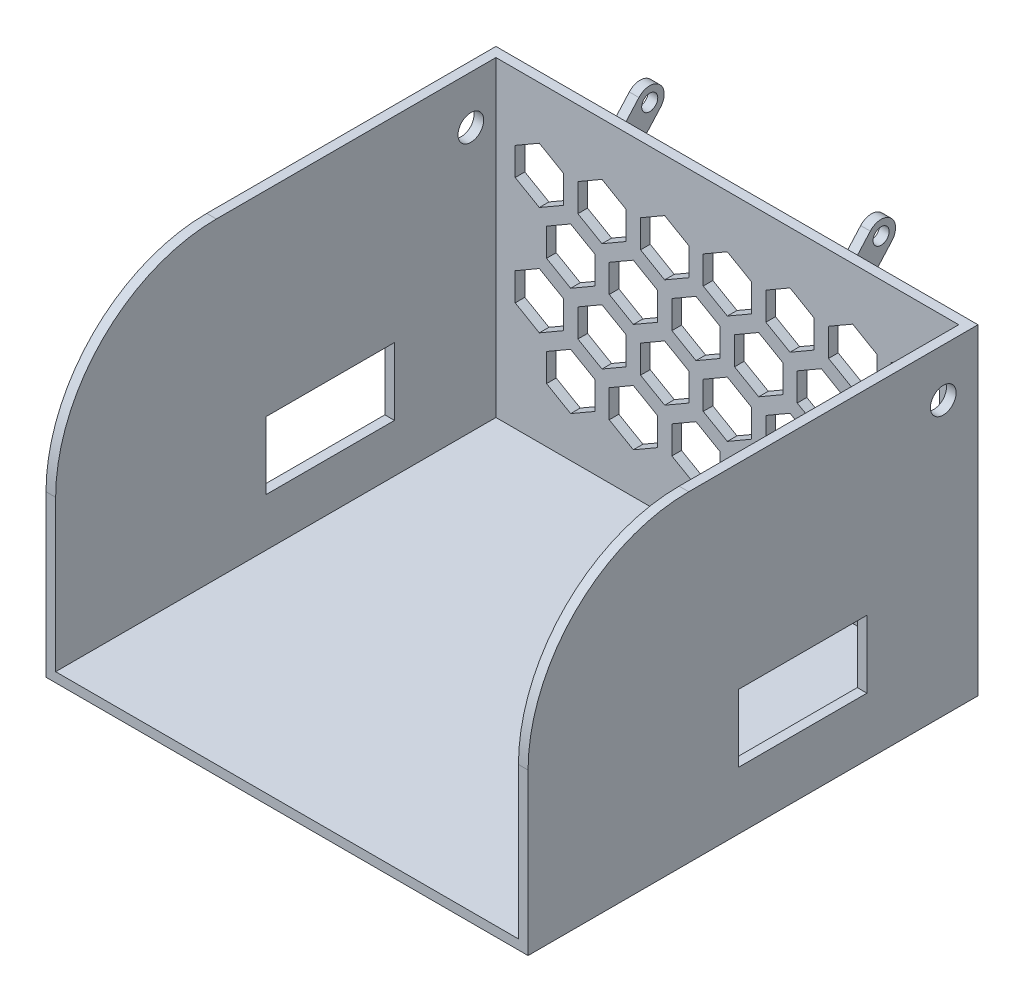
SolidWorks part; units mm, degrees
material "PLA"
ref_plane "Front Plane" through (0, 0, 0) normal (0, 0, 1) x (1, 0, 0)
ref_plane "Top Plane" through (0, 0, 0) normal (0, 1, 0) x (1, 0, 0)
ref_plane "Right Plane" through (0, 0, 0) normal (1, 0, 0) x (0, 0, -1)
sketch "Sketch1" plane through (0, 0, 0) normal (1, 0, 0) x (0, 0, -1)
  line L0 (0, 0) -> (-140, 0)
  line L1 (-140, 0) -> (-140, 50)
  line L2 (-90, 100) -> (0, 100)
  line L3 (0, 100) -> (0, 0)
  arc A0 (-140, 50) -> (-90, 100) centre (-90, 50) cw
  dimension "D1" = 140
  dimension "D2" = 100
  dimension "D3" = 50
extrude "Boss-Extrude1" add sketch "Sketch1" along normal blind 150 contours A0 L2 L3 L0 L1
sketch "Sketch2" plane through (0, 100, 0) normal (0, 1, 0) x (1, 0, 0)
  line L0 (150, 0) -> (0, 0) construction
  line L1 (3, -3) -> (147, -3)
  line L2 (3, -3) -> (3, -145)
  line L3 (3, -145) -> (147, -145)
  line L4 (147, -3) -> (147, -145)
  line L5 (150, -90) -> (150, 0) construction
  line L6 (0, -90) -> (0, 0) construction
  line L8 (150, -140) -> (0, -140) construction
  dimension "D1" = 3
  dimension "D2" = 3
  dimension "D3" = 3
  dimension "D4" = 5
extrude "Cut-Extrude1" cut sketch "Sketch2" against normal offset from surface (97 mm away) 3 up to face at (75, 0, 70)
ref_plane "Plane1" through (75, 0, 0) normal (1, 0, 0) x (0, 0, -1)
ref_plane "Plane2" through (111, 0, 0) normal (1, 0, 0) x (0, 0, -1)
ref_plane "Plane3" through (39, 0, 0) normal (1, 0, 0) x (0, 0, -1)
sketch "Sketch3" plane through (111, 0, 0) normal (1, 0, 0) x (0, 0, -1)
  line L0 (0, 100) -> (0, 86.4837)
  line L1 (0, 86.4837) -> (10.7098, 98.4837)
  line L2 (3.9952, 104.4764) -> (0, 100)
  arc A0 (10.7098, 98.4837) -> (3.9952, 104.4764) centre (7.3525, 101.4801) ccw
  circle A1 centre (7.3525, 101.4801) radius 2.5
  dimension "D1" = 2
  dimension "D2" = 5
  dimension "D3" = 6
  dimension "D4" = 12
extrude "Boss-Extrude2" add sketch "Sketch3" along normal mid plane 3
mirror "Mirror1" about plane through (75, 0, 0) normal (1, 0, 0) of "Boss-Extrude2"
sketch "Sketch4" plane through (150, 0, 0) normal (1, 0, 0) x (0, 0, -1)
  line L0 (-10.8107, 85.0634) -> (-67.3793, 28.4949) construction
  line L1 (-74.5612, 38.9949) -> (-74.5612, 17.9949)
  line L2 (-74.5612, 17.9949) -> (-34.5612, 17.9949)
  line L3 (0, 0) -> (-140, 0) construction
  line L4 (-34.5612, 17.9949) -> (-34.5612, 38.9949)
  line L5 (-34.5612, 38.9949) -> (-74.5612, 38.9949)
  circle A0 centre (-67.3793, 28.4949) radius 2.5
  circle A1 centre (-10.8107, 85.0634) radius 4
  point P8 (-74.5612, 28.4949)
  dimension "D4" = 8
  dimension "D5" = 5
  dimension "D1" = 80
  dimension "D2" = 45
  dimension "D3" = 40
  dimension "D6" = 21
extrude "Cut-Extrude2" cut sketch "Sketch4" against normal up to next contours A0 | A1 | L4 L5 A0 L1 L2 region at (150, 28.4949, 54.2544) region at (150, 28.4949, 67.3793) region at (150, 85.0634, 10.8107)
mirror "Mirror2" about plane through (75, 0, 0) normal (1, 0, 0) of "Cut-Extrude2"
sketch "Sketch5" plane through (0, 0, 0) normal (0, 0, -1) x (-1, 0, 0)
  line L0 (-150, 75) -> (0, 75) construction
  line L1 (-150, 100) -> (-150, 0) construction
  line L2 (0, 100) -> (0, 0) construction
  line L3 (-75, 100) -> (-75, 0) construction
  line L4 (-109.5, 100) -> (-40.5, 100) construction
  line L5 (-75, 91.3518) -> (-75, -91.3518) construction
  line L6 (-114, 83.6603) -> (-121.5, 79.3301)
  line L7 (-133.5, 83.6603) -> (-141, 79.3301)
  line L8 (-141, 79.3301) -> (-141, 70.6699)
  line L9 (-141, 70.6699) -> (-133.5, 66.3397)
  line L10 (-133.5, 66.3397) -> (-126, 70.6699)
  line L11 (-126, 70.6699) -> (-126, 79.3301)
  line L12 (-126, 79.3301) -> (-133.5, 83.6603)
  line L13 (-121.5, 79.3301) -> (-121.5, 70.6699)
  line L14 (-121.5, 70.6699) -> (-114, 66.3397)
  line L15 (-114, 66.3397) -> (-106.5, 70.6699)
  line L16 (-106.5, 70.6699) -> (-106.5, 79.3301)
  line L17 (-106.5, 79.3301) -> (-114, 83.6603)
  line L18 (-94.5, 83.6603) -> (-102, 79.3301)
  line L19 (-102, 79.3301) -> (-102, 70.6699)
  line L20 (-102, 70.6699) -> (-94.5, 66.3397)
  line L21 (-94.5, 66.3397) -> (-87, 70.6699)
  line L22 (-87, 70.6699) -> (-87, 79.3301)
  line L23 (-87, 79.3301) -> (-94.5, 83.6603)
  line L24 (-75, 83.6603) -> (-82.5, 79.3301)
  line L25 (-82.5, 79.3301) -> (-82.5, 70.6699)
  line L26 (-82.5, 70.6699) -> (-75, 66.3397)
  line L27 (-75, 66.3397) -> (-67.5, 70.6699)
  line L28 (-67.5, 70.6699) -> (-67.5, 79.3301)
  line L29 (-67.5, 79.3301) -> (-75, 83.6603)
  line L30 (-55.5, 83.6603) -> (-63, 79.3301)
  line L31 (-63, 79.3301) -> (-63, 70.6699)
  line L32 (-63, 70.6699) -> (-55.5, 66.3397)
  line L33 (-55.5, 66.3397) -> (-48, 70.6699)
  line L34 (-48, 70.6699) -> (-48, 79.3301)
  line L35 (-48, 79.3301) -> (-55.5, 83.6603)
  line L36 (-36, 83.6603) -> (-43.5, 79.3301)
  line L37 (-43.5, 79.3301) -> (-43.5, 70.6699)
  line L38 (-43.5, 70.6699) -> (-36, 66.3397)
  line L39 (-36, 66.3397) -> (-28.5, 70.6699)
  line L40 (-28.5, 70.6699) -> (-28.5, 79.3301)
  line L41 (-28.5, 79.3301) -> (-36, 83.6603)
  line L42 (-16.5, 83.6603) -> (-24, 79.3301)
  line L43 (-24, 79.3301) -> (-24, 70.6699)
  line L44 (-24, 70.6699) -> (-16.5, 66.3397)
  line L45 (-16.5, 66.3397) -> (-9, 70.6699)
  line L46 (-9, 70.6699) -> (-9, 79.3301)
  line L47 (-9, 79.3301) -> (-16.5, 83.6603)
  line L48 (-150, 58.1125) -> (0, 58.1125) construction
  line L49 (-123.75, 58.1125) -> (-123.75, 75) construction
  line L50 (-123.75, 66.7728) -> (-131.25, 62.4426)
  line L51 (-131.25, 62.4426) -> (-131.25, 53.7824)
  line L52 (-131.25, 53.7824) -> (-123.75, 49.4523)
  line L53 (-123.75, 49.4523) -> (-116.25, 53.7824)
  line L54 (-116.25, 53.7824) -> (-116.25, 62.4426)
  line L55 (-116.25, 62.4426) -> (-123.75, 66.7728)
  line L56 (-37.5, 100) -> (0, 100) construction
  line L57 (-104.25, 66.7728) -> (-111.75, 62.4426)
  line L58 (-111.75, 62.4426) -> (-111.75, 53.7824)
  line L59 (-111.75, 53.7824) -> (-104.25, 49.4523)
  line L60 (-104.25, 49.4523) -> (-96.75, 53.7824)
  line L61 (-96.75, 53.7824) -> (-96.75, 62.4426)
  line L62 (-96.75, 62.4426) -> (-104.25, 66.7728)
  line L63 (-84.75, 66.7728) -> (-92.25, 62.4426)
  line L64 (-92.25, 62.4426) -> (-92.25, 53.7824)
  line L65 (-92.25, 53.7824) -> (-84.75, 49.4523)
  line L66 (-84.75, 49.4523) -> (-77.25, 53.7824)
  line L67 (-77.25, 53.7824) -> (-77.25, 62.4426)
  line L68 (-77.25, 62.4426) -> (-84.75, 66.7728)
  line L69 (-65.25, 66.7728) -> (-72.75, 62.4426)
  line L70 (-72.75, 62.4426) -> (-72.75, 53.7824)
  line L71 (-72.75, 53.7824) -> (-65.25, 49.4523)
  line L72 (-65.25, 49.4523) -> (-57.75, 53.7824)
  line L73 (-57.75, 53.7824) -> (-57.75, 62.4426)
  line L74 (-57.75, 62.4426) -> (-65.25, 66.7728)
  line L75 (-45.75, 66.7728) -> (-53.25, 62.4426)
  line L76 (-53.25, 62.4426) -> (-53.25, 53.7824)
  line L77 (-53.25, 53.7824) -> (-45.75, 49.4523)
  line L78 (-45.75, 49.4523) -> (-38.25, 53.7824)
  line L79 (-38.25, 53.7824) -> (-38.25, 62.4426)
  line L80 (-38.25, 62.4426) -> (-45.75, 66.7728)
  line L81 (-26.25, 66.7728) -> (-33.75, 62.4426)
  line L82 (-33.75, 62.4426) -> (-33.75, 53.7824)
  line L83 (-33.75, 53.7824) -> (-26.25, 49.4523)
  line L84 (-26.25, 49.4523) -> (-18.75, 53.7824)
  line L85 (-18.75, 53.7824) -> (-18.75, 62.4426)
  line L86 (-18.75, 62.4426) -> (-26.25, 66.7728)
  line L87 (-9, 36.8949) -> (-16.5, 32.5648)
  line L88 (-9, 45.5551) -> (-9, 36.8949)
  line L89 (-16.5, 49.8853) -> (-9, 45.5551)
  line L90 (-24, 45.5551) -> (-16.5, 49.8853)
  line L91 (-24, 36.8949) -> (-24, 45.5551)
  line L92 (-16.5, 32.5648) -> (-24, 36.8949)
  line L93 (-28.5, 36.8949) -> (-36, 32.5648)
  line L94 (-28.5, 45.5551) -> (-28.5, 36.8949)
  line L95 (-36, 49.8853) -> (-28.5, 45.5551)
  line L96 (-43.5, 45.5551) -> (-36, 49.8853)
  line L97 (-43.5, 36.8949) -> (-43.5, 45.5551)
  line L98 (-36, 32.5648) -> (-43.5, 36.8949)
  line L99 (-48, 36.8949) -> (-55.5, 32.5648)
  line L100 (-48, 45.5551) -> (-48, 36.8949)
  line L101 (-55.5, 49.8853) -> (-48, 45.5551)
  line L102 (-63, 45.5551) -> (-55.5, 49.8853)
  line L103 (-63, 36.8949) -> (-63, 45.5551)
  line L104 (-55.5, 32.5648) -> (-63, 36.8949)
  line L105 (-67.5, 36.8949) -> (-75, 32.5648)
  line L106 (-67.5, 45.5551) -> (-67.5, 36.8949)
  line L107 (-75, 49.8853) -> (-67.5, 45.5551)
  line L108 (-82.5, 45.5551) -> (-75, 49.8853)
  line L109 (-82.5, 36.8949) -> (-82.5, 45.5551)
  line L110 (-75, 32.5648) -> (-82.5, 36.8949)
  line L111 (-87, 36.8949) -> (-94.5, 32.5648)
  line L112 (-87, 45.5551) -> (-87, 36.8949)
  line L113 (-94.5, 49.8853) -> (-87, 45.5551)
  line L114 (-102, 45.5551) -> (-94.5, 49.8853)
  line L115 (-102, 36.8949) -> (-102, 45.5551)
  line L116 (-94.5, 32.5648) -> (-102, 36.8949)
  line L117 (-106.5, 36.8949) -> (-114, 32.5648)
  line L118 (-106.5, 45.5551) -> (-106.5, 36.8949)
  line L119 (-114, 49.8853) -> (-106.5, 45.5551)
  line L120 (-121.5, 45.5551) -> (-114, 49.8853)
  line L121 (-121.5, 36.8949) -> (-121.5, 45.5551)
  line L122 (-114, 32.5648) -> (-121.5, 36.8949)
  line L123 (-126, 36.8949) -> (-133.5, 32.5648)
  line L124 (-126, 45.5551) -> (-126, 36.8949)
  line L125 (-133.5, 49.8853) -> (-126, 45.5551)
  line L126 (-141, 45.5551) -> (-133.5, 49.8853)
  line L127 (-141, 36.8949) -> (-141, 45.5551)
  line L128 (-133.5, 32.5648) -> (-141, 36.8949)
  line L129 (-141, 41.225) -> (-9, 41.225) construction
  line L130 (-18.75, 20.0074) -> (-26.25, 15.6773)
  line L131 (-18.75, 28.6676) -> (-18.75, 20.0074)
  line L132 (-26.25, 32.9978) -> (-18.75, 28.6676)
  line L133 (-33.75, 28.6676) -> (-26.25, 32.9978)
  line L134 (-33.75, 20.0074) -> (-33.75, 28.6676)
  line L135 (-26.25, 15.6773) -> (-33.75, 20.0074)
  line L136 (-38.25, 20.0074) -> (-45.75, 15.6773)
  line L137 (-38.25, 28.6676) -> (-38.25, 20.0074)
  line L138 (-45.75, 32.9978) -> (-38.25, 28.6676)
  line L139 (-53.25, 28.6676) -> (-45.75, 32.9978)
  line L140 (-53.25, 20.0074) -> (-53.25, 28.6676)
  line L141 (-45.75, 15.6773) -> (-53.25, 20.0074)
  line L142 (-57.75, 20.0074) -> (-65.25, 15.6773)
  line L143 (-57.75, 28.6676) -> (-57.75, 20.0074)
  line L144 (-65.25, 32.9978) -> (-57.75, 28.6676)
  line L145 (-72.75, 28.6676) -> (-65.25, 32.9978)
  line L146 (-72.75, 20.0074) -> (-72.75, 28.6676)
  line L147 (-65.25, 15.6773) -> (-72.75, 20.0074)
  line L148 (-77.25, 20.0074) -> (-84.75, 15.6773)
  line L149 (-77.25, 28.6676) -> (-77.25, 20.0074)
  line L150 (-84.75, 32.9978) -> (-77.25, 28.6676)
  line L151 (-92.25, 28.6676) -> (-84.75, 32.9978)
  line L152 (-92.25, 20.0074) -> (-92.25, 28.6676)
  line L153 (-84.75, 15.6773) -> (-92.25, 20.0074)
  line L154 (-96.75, 20.0074) -> (-104.25, 15.6773)
  line L155 (-96.75, 28.6676) -> (-96.75, 20.0074)
  line L156 (-104.25, 32.9978) -> (-96.75, 28.6676)
  line L157 (-111.75, 28.6676) -> (-104.25, 32.9978)
  line L158 (-111.75, 20.0074) -> (-111.75, 28.6676)
  line L159 (-104.25, 15.6773) -> (-111.75, 20.0074)
  line L160 (-116.25, 20.0074) -> (-123.75, 15.6773)
  line L161 (-116.25, 28.6676) -> (-116.25, 20.0074)
  line L162 (-123.75, 32.9978) -> (-116.25, 28.6676)
  line L163 (-131.25, 28.6676) -> (-123.75, 32.9978)
  line L164 (-131.25, 20.0074) -> (-131.25, 28.6676)
  line L165 (-123.75, 15.6773) -> (-131.25, 20.0074)
  circle A0 centre (-133.5, 75) radius 7.5 construction
  circle A1 centre (-123.75, 58.1125) radius 7.5 construction
  point P71 (-120, 64.6077)
  point P72 (-117.75, 68.5048)
  dimension "D2" = 15
  dimension "D3" = 9
  dimension "D4" = 9
  dimension "D5" = 25
  dimension "D6" = 4.5
  dimension "D8" = 18.75
  dimension "D1" = 7
  dimension "D7" = 6
extrude "Cut-Extrude3" cut sketch "Sketch5" against normal blind 10
equation "\"forward_length\"= 130"
equation "\"height\"= 100"
equation "\"eslabon_AB\"=80"
